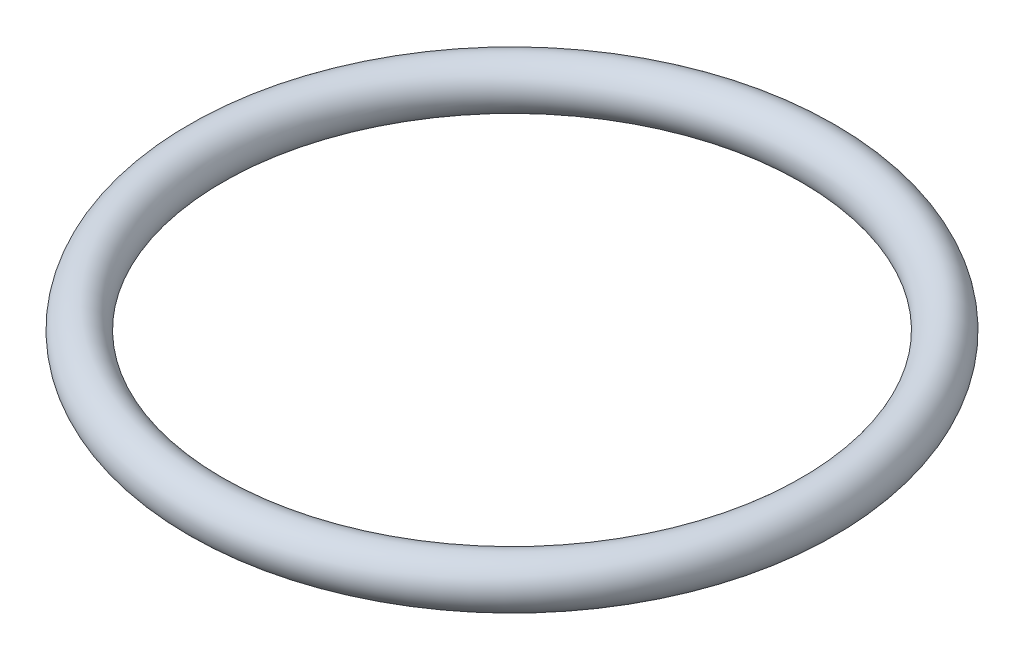
SolidWorks part; units mm, degrees
material "Rubber"
ref_plane "Front Plane" through (0, 0, 0) normal (0, 0, 1) x (1, 0, 0)
ref_plane "Top Plane" through (0, 0, 0) normal (0, 1, 0) x (1, 0, 0)
ref_plane "Right Plane" through (0, 0, 0) normal (1, 0, 0) x (0, 0, -1)
sketch "Sketch1" plane through (0, 0, 0) normal (0, 1, 0) x (1, 0, 0)
  line L0 (0, 0) -> (-22.225, 0) construction
  line L1 (0, 0) -> (22.225, 0) construction
  line L2 (-22.225, 0) -> (-19.05, 0) construction
  line L3 (19.05, 0) -> (22.225, 0) construction
  circle A0 centre (0, 0) radius 19.05 construction
  circle A1 centre (0, 0) radius 22.225 construction
  circle A2 centre (0, 0) radius 20.6375 construction
sketch "Sketch4" plane through (0, 0, 0) normal (0, 0, 1) x (1, 0, 0)
  line L0 (-22.225, 0) -> (-19.05, 0) construction
  circle A0 centre (-20.6375, 0) radius 1.5875
sketch "Sketch5" plane through (0, 0, 0) normal (1, 0, 0) x (0, 0, -1)
  line L0 (0, 0) -> (0, 9.9715) construction
revolve "Revolve1" add sketch "Sketch4" angle 360 about L0
ref_plane "Plane1" through (0, -1.5875, 0) normal (0, 1, 0) x (1, 0, 0)
ref_axis "Axis1" through (0, 0, 0) along (0, 1, 0)
